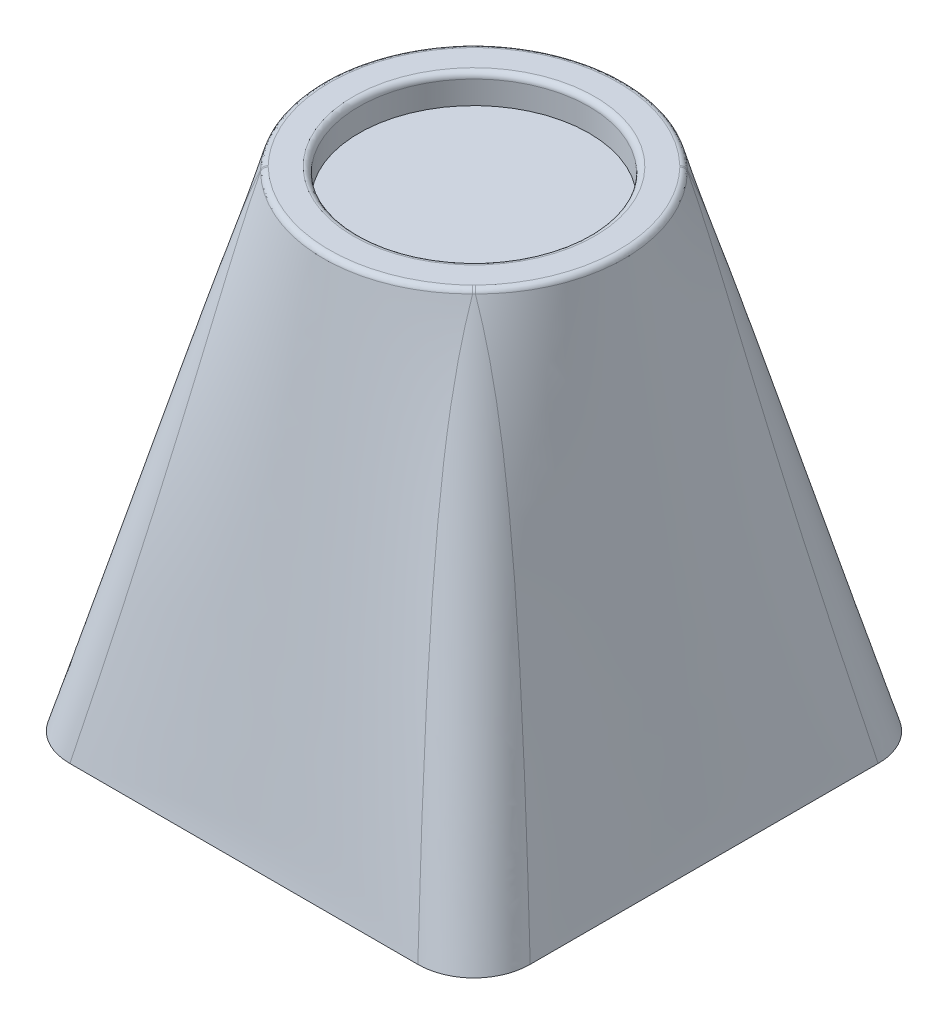
SolidWorks part; units mm, degrees
ref_plane "Front Plane" through (0, 0, 0) normal (0, 0, 1) x (1, 0, 0)
ref_plane "Top Plane" through (0, 0, 0) normal (0, 1, 0) x (1, 0, 0)
ref_plane "Right Plane" through (0, 0, 0) normal (1, 0, 0) x (0, 0, -1)
sketch "Sketch1" plane through (0, 0, 0) normal (0, 1, 0) x (1, 0, 0)
  line L1 (0, 0) -> (80, 0)
  line L2 (0, 0) -> (0, 80)
  line L3 (0, 80) -> (80, 80)
  line L4 (80, 0) -> (80, 80)
  dimension "D1" = 80
ref_plane "Plane1" through (0, 85, 0) normal (0, 1, 0) x (1, 0, 0)
sketch "Sketch2" plane through (0, 85, 0) normal (0, 1, 0) x (1, 0, 0)
  line L0 (40, 40) -> (80, 40) construction
  line L1 (80, 0) -> (80, 80) construction
  line L2 (40, 40) -> (40, 80) construction
  line L3 (0, 80) -> (80, 80) construction
  line L4 (40, 40) -> (0, 40) construction
  line L5 (0, 0) -> (0, 80) construction
  circle A0 centre (40, 40) radius 26
  dimension "D1" = 52
loft "Loft1" add profiles "Sketch1", "Sketch2"
sketch "Sketch3" plane through (0, 85, 0) normal (0, 1, 0) x (1, 0, 0)
  circle A0 centre (40, 40) radius 20
  circle A1 centre (40, 40) radius 26 construction
  dimension "D1" = 40
extrude "Cut-Extrude1" cut sketch "Sketch3" against normal blind 5
fillet "Fillet1" radius 10 4 edges
fillet "Fillet2" radius 1 5 edges at (40, 85, -20)
sketch "Sketch4" plane through (0, 0, 0) normal (0, -1, 0) x (1, 0, 0)
  line L2 (9.7679, 0) -> (70.2321, 0) construction
  line L3 (30, -20) -> (50, -20)
  line L4 (20, -30) -> (20, -50)
  line L5 (30, -60) -> (50, -60)
  line L6 (60, -30) -> (60, -50)
  line L7 (80, -9.7679) -> (80, -70.2321) construction
  line L8 (0, -70.2321) -> (0, -9.7679) construction
  arc A0 (20, -50) -> (30, -60) centre (30, -50) ccw
  arc A1 (50, -60) -> (60, -50) centre (50, -50) ccw
  arc A2 (50, -20) -> (60, -30) centre (50, -30) cw
  arc A3 (30, -20) -> (20, -30) centre (30, -30) ccw
  dimension "D4" = 10
  dimension "D1" = 20
  dimension "D2" = 20
  dimension "D3" = 20
extrude "Cut-Extrude2" cut sketch "Sketch4" against normal blind 50
